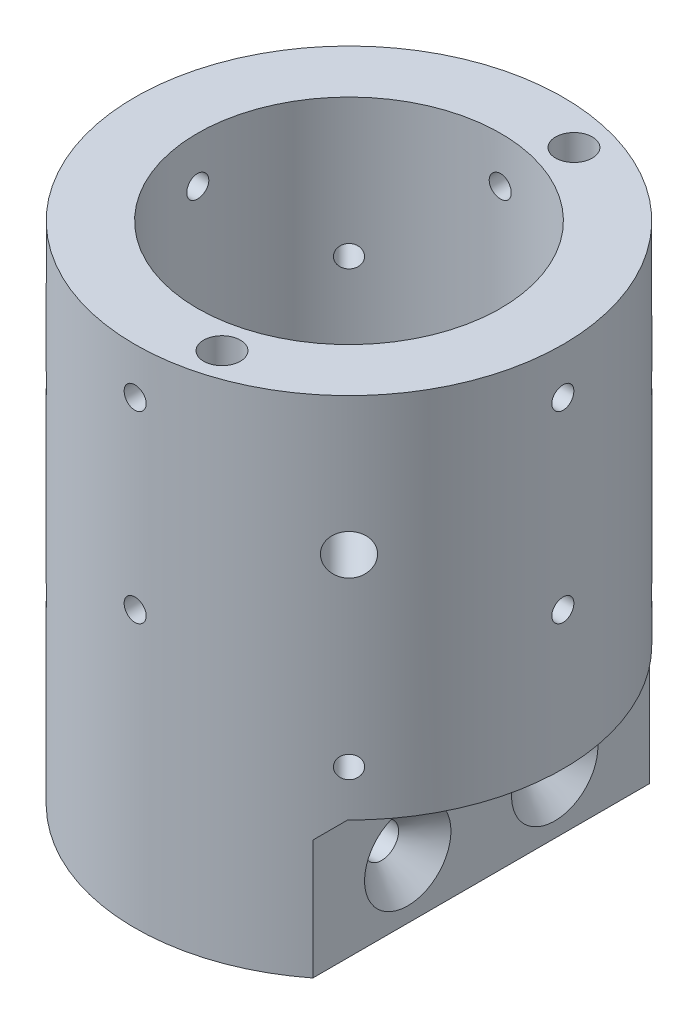
SolidWorks part; units mm, degrees
ref_plane "Спереди" through (0, 0, 0) normal (0, 0, 1) x (1, 0, 0)
ref_plane "Сверху" through (0, 0, 0) normal (0, 1, 0) x (1, 0, 0)
ref_plane "Справа" through (0, 0, 0) normal (1, 0, 0) x (0, 0, -1)
sketch "Эскиз1" plane through (0, 0, 0) normal (0, 1, 0) x (1, 0, 0)
  circle A0 centre (0, 0) radius 23.3
  dimension "D1" = 46.6
extrude "Бобышка-Вытянуть1" add sketch "Эскиз1" along normal blind 5
sketch "Эскиз2" plane through (0, 5, 0) normal (0, 1, 0) x (1, 0, 0)
  circle A0 centre (0, 0) radius 23.3
  circle A1 centre (0, 0) radius 16.5
  circle A2 centre (0, 0) radius 23.3 construction
  dimension "D1" = 33
  dimension "D2" = 0
extrude "Бобышка-Вытянуть2" add sketch "Эскиз2" along normal blind 35
chamfer "Фаска8" distance 2 angle 45 1 edges at (0, 5, 16.5)
sketch "Эскиз3" plane through (0, 0, 0) normal (1, 0, 0) x (0, 0, -1)
  line L0 (-23.3, 20) -> (28.0263, 20) construction
  line L1 (-23.3, 40) -> (-23.3, 0) construction
  line L2 (16.5, 40) -> (-16.5, 40) construction
  circle A1 centre (0, 35) radius 1.2
  dimension "D1" = 2.4
  dimension "D2" = 5
extrude "Вырез-Вытянуть1" cut sketch "Эскиз3" against normal through all
ref_plane "Плоскость1" through (0, 0, 0) normal (0.7071, 0, 0.7071) x (0, -1, 0)
sketch "Эскиз4" plane through (0, 0, 0) normal (0.7071, 0, 0.7071) x (0, -1, 0)
  line L0 (-20, 23.3) -> (-20, -30.0625) construction
  line L1 (0, 23.3) -> (-40, 23.3) construction
  line L3 (0, -23.3) -> (0, 23.3) construction
  circle A1 centre (-5, 0) radius 1.2
  dimension "D1" = 5
  dimension "D2" = 2.4
extrude "Вырез-Вытянуть2" cut sketch "Эскиз4" against normal through all from offset 16.3 offset against normal yes
pattern_circular "Круговой массив1" count 4 over 360 about axis through (0, 5, 0) along (0, -1, 0) of "Вырез-Вытянуть2"
pattern_circular "Круговой массив2" count 4 over 360 about axis through (0, 5, 0) along (0, -1, 0) of "Вырез-Вытянуть1"
pattern_linear "Линейный массив3" count 2 spacing 20 along (0, 1, 0) of "Круговой массив1"
pattern_linear "Линейный массив4" count 2 spacing 20 along (0, -1, 0) of "Круговой массив2"
sketch "Эскиз12" plane through (0, 0, 0) normal (0, -1, 0) x (1, 0, 0)
  line L1 (14.3923, 18.3235) -> (14.3923, -18.3235)
  line L20 (0, 15) -> (-2.7835, 17.7835)
  line L21 (-2.7835, -17.7835) -> (0, -15)
  line L22 (0, -15) -> (0, 15)
  line L23 (0, 15) -> (-2.7835, 17.7835)
  line L24 (-2.7835, -17.7835) -> (0, -15)
  line L25 (0, -15) -> (0, 15)
  circle A6 centre (0, 0) radius 23.3 construction
  arc A7 (14.3923, 18.3235) -> (14.3923, -18.3235) centre (0, 0) ccw
  arc A13 (-2.7835, 17.7835) -> (-2.7835, -17.7835) centre (0, 0) ccw
  arc A14 (-2.7835, 17.7835) -> (-2.7835, -17.7835) centre (0, 0) ccw
  dimension "D1" = 0
extrude "Бобышка-Вытянуть3" add sketch "Эскиз12" along normal blind 15 contours L1 region at (13.7929, 0, 0)
sketch "Эскиз13" plane through (0, -15, 0) normal (0, -1, 0) x (1, 0, 0)
  line L14 (-2.6786, -18.1029) -> (0.3, -15.1243)
  line L15 (0.3, 15.1243) -> (-2.6786, 18.1029)
  line L16 (0.3, -15.1243) -> (0.3, 15.1243)
  line L17 (-2.6786, -18.1029) -> (0.3, -15.1243)
  line L18 (0.3, 15.1243) -> (-2.6786, 18.1029)
  line L19 (0.3, -15.1243) -> (0.3, 15.1243)
  arc A5 (-2.6786, 18.1029) -> (-2.6786, -18.1029) centre (0, 0) ccw
  arc A6 (-2.6786, 18.1029) -> (-2.6786, -18.1029) centre (0, 0) ccw
  dimension "D1" = 0.3
extrude "Вырез-Вытянуть10" cut sketch "Эскиз13" against normal up to surface (15 mm away) up to face at (18.8461, 0, 0)
chamfer "Фаска4" distance 2 angle 45 1 edges at (14.3923, 0, 0)
chamfer "Фаска6" distance 2 angle 45 4 edges at (-1.1893, 0, -16.6136) (-18.3, 0, 0) (0.3, 0, 0) (-1.1893, 0, 16.6136)
chamfer "Фаска7" distance 2 angle 45 4 edges at (-1.1893, -15, -16.6136) (-18.3, -15, 0) (-1.1893, -15, 16.6136) (0.3, -15, 0)
hole_wizard "Зенковка для винта с полупотайной головкой M41" positions "Эскиз14" profile "Эскиз15" countersink size "M4" standard "ISO" end condition through all
sketch "Эскиз14" plane through (14.3923, -676.2045, -24.0267) normal (1, 0, 0) x (0, 0.0202, -0.9998)
  line L0 (-10.4265, 674.5519) -> (-10.6887, 661.5545) construction
  line L4 (-10.5576, 668.0532) -> (-20.4413, 668.0532) construction
  line L5 (-20.4413, 668.0532) -> (-1.8045, 668.0532) construction
  point P0 (-18.5576, 668.0532)
  point P19 (-2.5641, 667.7306)
sketch "Эскиз15" plane through (14.3923, -8.6613, 7.9984) normal (0, 1, 0) x (0, 0, -1)
  line L0 (0, 0) -> (0, 37.6923)
  line L1 (0, 37.6923) -> (1.85, 37.6923)
  line L2 (1.85, 37.6923) -> (1.85, 2.85)
  line L3 (1.85, 2.85) -> (4.7, 0)
  line L4 (4.7, 0) -> (0, 0)
  line L5 (-1.85, 2.85) -> (-4.7, 0) construction
  line L6 (0, -6.35) -> (0, 107.95) construction
  dimension "Диаметр сквозного отверстия" = 3.7
  dimension "Глубина сквозного отверстия" = 37.6923
  dimension "Диаметр передней зенковки" = 9.4
  dimension "Угол передней зенковки" = 90
sketch "Эскиз17" plane through (0, -15, 0) normal (0, -1, 0) x (1, 0, 0)
  circle A0 centre (5.3288, 0) radius 2.5
extrude "Вырез-Вытянуть11" cut sketch "Эскиз17" against normal blind 86
ref_plane "Плоскость2" through (0, 0, 0) normal (-0.7071, 0, -0.7071) x (-0.7071, 0, 0.7071)
sketch "Эскиз18" plane through (0, 0, 0) normal (-0.7071, 0, -0.7071) x (-0.7071, 0, 0.7071)
  circle A0 centre (0, 25) radius 1.2 construction
  circle A1 centre (0, 25) radius 1.2
  circle A2 centre (0, 25) radius 2.2
extrude "Вырез-Вытянуть12" cut sketch "Эскиз18" against normal blind 86
sketch "Эскиз21" plane through (0, -15, 0) normal (0, -1, 0) x (1, 0, 0)
  line L0 (5.3288, -15.6158) -> (5.3288, -22.6825) construction
  circle A0 centre (5.3288, -19.1491) radius 2
  circle A1 centre (0, 0) radius 16.5 construction
  circle A2 centre (0, 0) radius 16.5 construction
  arc A3 (14.3923, 18.3235) -> (14.3923, -18.3235) centre (0, 0) ccw construction
  point P5 (5.3288, -22.6825)
  point P10 (0, 0)
  point P13 (5.3288, -19.0114)
  point P14 (0, 0)
extrude "Вырез-Вытянуть13" cut sketch "Эскиз21" against normal through all
mirror "Зеркальное отражение1" about plane through (0, 0, 0) normal (0, 0, 1) of "Вырез-Вытянуть13"
